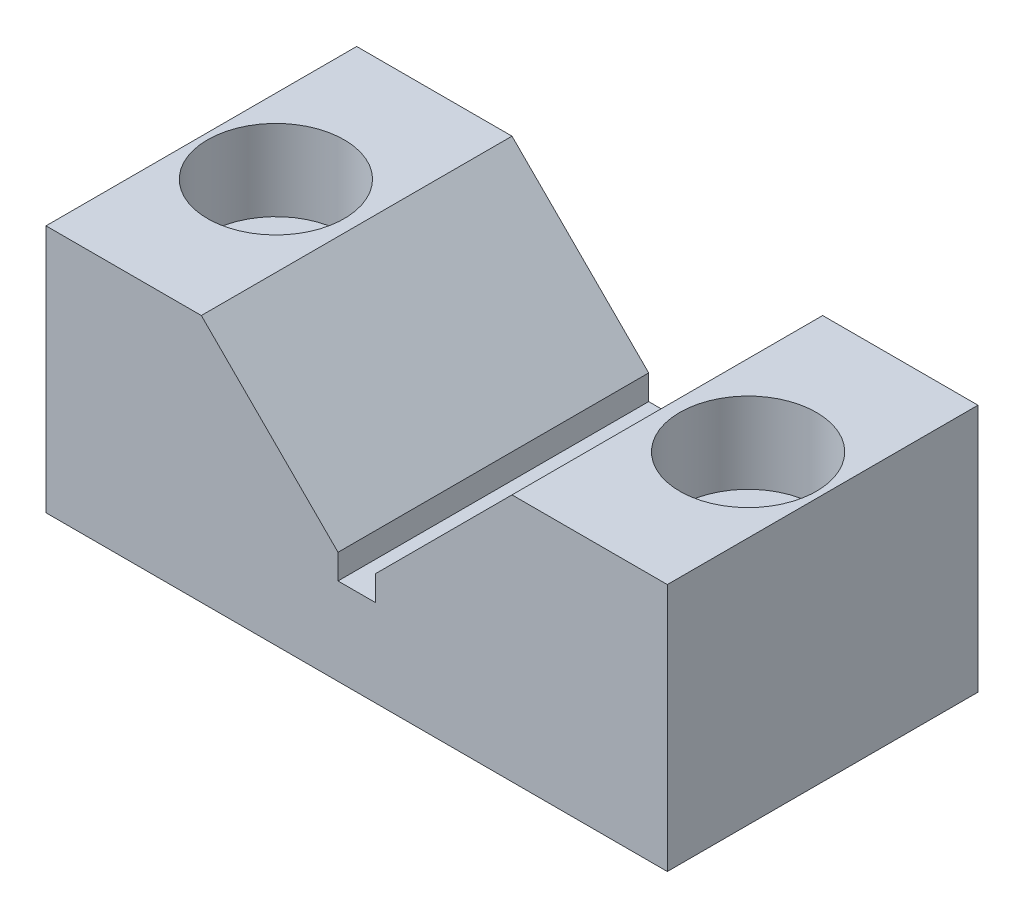
SolidWorks part; units mm, degrees
material "AISI 1045 Steel, cold drawn"
ref_plane "Front Plane" through (0, 0, 0) normal (0, 0, 1) x (1, 0, 0)
ref_plane "Top Plane" through (0, 0, 0) normal (0, 1, 0) x (1, 0, 0)
ref_plane "Right Plane" through (0, 0, 0) normal (1, 0, 0) x (0, 0, -1)
sketch "Sketch1" plane through (0, 0, 0) normal (0, 0, 1) x (1, 0, 0)
  line L0 (-25, 0) -> (25, 0)
  line L1 (25, 0) -> (25, 20)
  line L2 (25, 20) -> (12.5, 20)
  line L3 (12.5, 20) -> (1.5, 9)
  line L4 (1.5, 9) -> (1.5, 7)
  line L5 (1.5, 7) -> (-1.5, 7)
  line L6 (-1.5, 7) -> (-1.5, 9)
  line L7 (-1.5, 9) -> (-12.5, 20)
  line L8 (-12.5, 20) -> (-25, 20)
  line L9 (-25, 20) -> (-25, 0)
  line L10 (0, 0) -> (0, 27.7172) construction
  dimension "D1" = 50
  dimension "D2" = 20
  dimension "D3" = 25
  dimension "D4" = 2
  dimension "D5" = 3
extrude "Boss-Extrude1" add sketch "Sketch1" along normal blind 12.5 and the other way blind 12.5
sketch "Sketch2" plane through (0, 20, 0) normal (0, 1, 0) x (-1, 0, 0)
  line L0 (19, 0) -> (-19, 0) construction
  line L1 (0, 18.4671) -> (0, 0) construction
  circle A0 centre (19, 0) radius 3.25
  circle A1 centre (-19, 0) radius 3.25
  dimension "D1" = 6.5
  dimension "D2" = 38
extrude "Cut-Extrude1" cut sketch "Sketch2" against normal through all
sketch "Sketch3" plane through (0, 20, 0) normal (0, 1, 0) x (-1, 0, 0)
  circle A0 centre (19, 0) radius 5.5
  circle A1 centre (-19, 0) radius 5.5
  circle A2 centre (-19, 0) radius 3.25 construction
  circle A3 centre (19, 0) radius 3.25 construction
  dimension "D1" = 11
extrude "Cut-Extrude2" cut sketch "Sketch3" against normal blind 6.5
